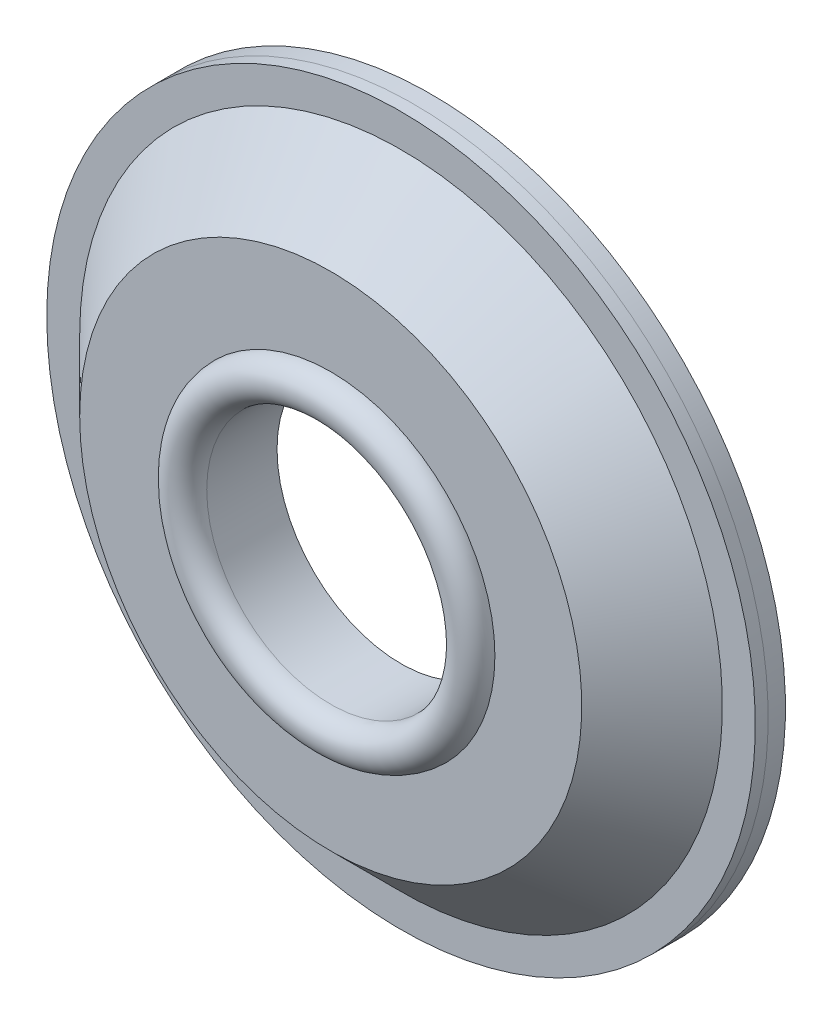
SolidWorks part; units mm, degrees
ref_plane "Front Plane" through (0, 0, 0) normal (0, 0, 1) x (1, 0, 0)
ref_plane "Top Plane" through (0, 0, 0) normal (0, 1, 0) x (1, 0, 0)
ref_plane "Right Plane" through (0, 0, 0) normal (1, 0, 0) x (0, 0, -1)
sketch "Sketch1" plane through (0, 0, 0) normal (0, 1, 0) x (1, 0, 0)
  line L0 (2.45, 0) -> (3.5613, 0)
  line L1 (-7.7, 0) -> (7.7, 0) construction
  line L13 (2.45, 0) -> (-2.45, 0) construction
  line L21 (7, 0) -> (6.3491, 0)
  line L24 (7, 0) -> (-7, 0) construction
  line L25 (4.3834, 0) -> (4.3834, 0.9827) construction
  line L26 (7, 0) -> (7, 0.254)
  line L35 (6.2439, 0.254) -> (7, 0.254) construction
  line L36 (4.8549, -1.1351) -> (6.2439, 0.254) construction
  line L37 (2.704, -1.1351) -> (4.8549, -1.1351) construction
  line L38 (2.704, -1.3891) -> (2.704, -1.1351) construction
  line L39 (3.2438, -1.3891) -> (2.704, -1.3891) construction
  line L41 (7, 0.5953) -> (7, 0.254)
  line L42 (4.9601, -1.3891) -> (3.2438, -1.3891)
  line L43 (6.3491, 0) -> (4.9601, -1.3891)
  line L44 (5.8094, 0.5953) -> (7, 0.5953)
  line L45 (4.9601, -0.254) -> (5.8094, 0.5953)
  line L46 (4.3834, 0.9827) -> (4.9601, -0.254)
  line L47 (3.6291, -0.635) -> (4.3834, 0.9827)
  line L48 (3.5613, -0.635) -> (3.6291, -0.635)
  line L49 (2.45, -1.3891) -> (2.45, 0)
  line L50 (3.5613, -0.635) -> (3.5613, 0)
  arc A2 (2.45, -1.3891) -> (3.2438, -1.3891) centre (2.8469, -1.3891) ccw
  point P6 (2.8469, -1.7859)
  point P16 (0, 0)
  point P20 (0, 0)
  point P36 (4.3834, 0)
  dimension "ID" = 4.9
  dimension "OD" = 14
  dimension "D1" = 0.254
  dimension "D2" = 45
  dimension "D4" = 2.7686
  dimension "D5" = 0.5953
  dimension "D7" = 1.1906
  dimension "D8" = 0.635
  dimension "D9" = 50
  dimension "D10" = 25
  dimension "D11" = 0.254
  dimension "D12" = 0.254
  dimension "D13" = 0.254
  dimension "D14" = 0.381
  dimension "D6" = 0.7938
  dimension "D15" = 0.3175
  dimension "D3" = 1.9844
ref_axis "Axis1" through (0, 0, -2.085) along (0, 0, 1)
sketch "Sketch2" plane through (0, 0, 0) normal (0, 1, 0) x (1, 0, 0)
  line L0 (3.2438, -1.3891) -> (2.704, -1.3891) construction
  line L1 (4.9601, -1.3891) -> (3.2438, -1.3891) construction
  line L2 (6.3491, 0) -> (4.9601, -1.3891) construction
  line L3 (7, 0) -> (6.3491, 0) construction
  line L4 (7, 0) -> (7, 0.254) construction
  line L5 (6.2439, 0.254) -> (7, 0.254) construction
  line L6 (4.8549, -1.1351) -> (6.2439, 0.254) construction
  line L7 (2.704, -1.1351) -> (4.8549, -1.1351) construction
  line L8 (2.704, -1.3891) -> (2.704, -1.1351) construction
  line L9 (3.2438, -1.3891) -> (2.704, -1.3891)
  line L10 (4.9601, -1.3891) -> (3.2438, -1.3891)
  line L11 (6.3491, 0) -> (4.9601, -1.3891)
  line L12 (7, 0) -> (6.3491, 0)
  line L13 (7, 0) -> (7, 0.254)
  line L14 (6.2439, 0.254) -> (7, 0.254)
  line L15 (4.8549, -1.1351) -> (6.2439, 0.254)
  line L16 (2.704, -1.1351) -> (4.8549, -1.1351)
  line L17 (2.704, -1.3891) -> (2.704, -1.1351)
sketch "Sketch3" plane through (0, 0, 0) normal (0, 1, 0) x (1, 0, 0)
  line L0 (2.45, -1.3891) -> (2.45, 0) construction
  line L1 (2.45, 0) -> (3.5613, 0) construction
  line L2 (3.5613, -0.635) -> (3.5613, 0) construction
  line L3 (3.5613, -0.635) -> (3.6291, -0.635) construction
  line L4 (3.6291, -0.635) -> (4.3834, 0.9827) construction
  line L5 (4.3834, 0.9827) -> (4.9601, -0.254) construction
  line L6 (4.9601, -0.254) -> (5.8094, 0.5953) construction
  line L7 (5.8094, 0.5953) -> (7, 0.5953) construction
  line L8 (7, 0.5953) -> (7, 0.254) construction
  line L9 (6.2439, 0.254) -> (7, 0.254) construction
  line L10 (4.8549, -1.1351) -> (6.2439, 0.254) construction
  line L11 (2.704, -1.1351) -> (4.8549, -1.1351) construction
  line L12 (2.704, -1.3891) -> (2.704, -1.1351) construction
  line L13 (3.2438, -1.3891) -> (2.704, -1.3891) construction
  line L14 (2.45, -1.3891) -> (2.45, 0)
  line L15 (2.45, 0) -> (3.5613, 0)
  line L16 (3.5613, -0.635) -> (3.5613, 0)
  line L17 (3.5613, -0.635) -> (3.6291, -0.635)
  line L18 (3.6291, -0.635) -> (4.3834, 0.9827)
  line L19 (4.3834, 0.9827) -> (4.9601, -0.254)
  line L20 (4.9601, -0.254) -> (5.8094, 0.5953)
  line L21 (5.8094, 0.5953) -> (7, 0.5953)
  line L22 (7, 0.5953) -> (7, 0.254)
  line L23 (6.2439, 0.254) -> (7, 0.254)
  line L24 (4.8549, -1.1351) -> (6.2439, 0.254)
  line L25 (2.704, -1.1351) -> (4.8549, -1.1351)
  line L26 (2.704, -1.3891) -> (2.704, -1.1351)
  line L27 (3.2438, -1.3891) -> (2.704, -1.3891)
  arc A0 (2.45, -1.3891) -> (3.2438, -1.3891) centre (2.8469, -1.3891) ccw construction
  arc A1 (2.45, -1.3891) -> (3.2438, -1.3891) centre (2.8469, -1.3891) ccw
revolve "Revolve1" add sketch "Sketch2" angle 360 about axis through (0, 0, -2.085) along (0, 0, 1)
revolve "Revolve2" add sketch "Sketch3" angle 360 about axis through (0, 0, -2.085) along (0, 0, 1)
ref_plane "Contact Plane 1" through (0, 0, -0.5953) normal (0, 0, -1) x (-1, 0, 0)
ref_plane "Contact Plane 2" through (0, 0, 1.3891) normal (0, 0, 1) x (1, 0, 0)
ref_axis "Center Axis 1" through (0, 0, 1.3891) along (0, 0, -1)
equation "\"D11@Sketch1\"=\"D1@Sketch1\""
equation "\"D12@Sketch1\"=\"D1@Sketch1\""
